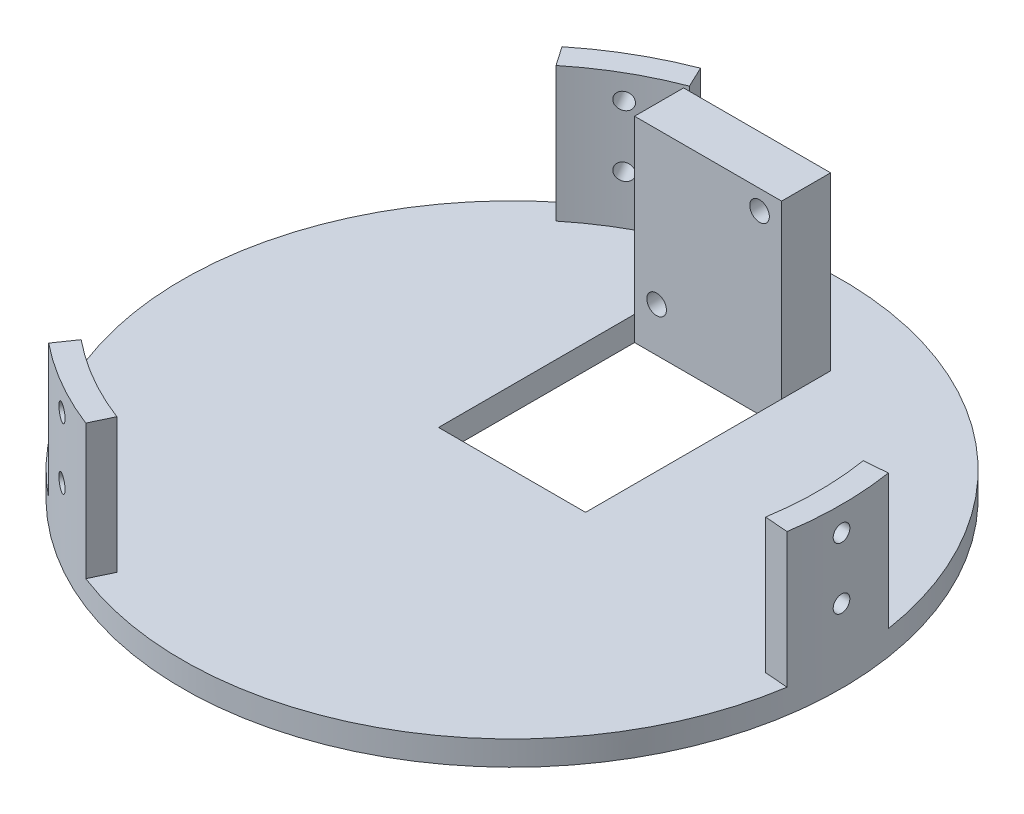
SolidWorks part; units mm, degrees
material "6061-T6 (SS)"
ref_plane "Front" through (0, 0, 0) normal (0, 0, 1) x (1, 0, 0)
ref_plane "Top" through (0, 0, 0) normal (0, 1, 0) x (1, 0, 0)
ref_plane "Right" through (0, 0, 0) normal (1, 0, 0) x (0, 0, -1)
sketch "Sketch1" plane through (0, 0, 0) normal (0, 1, 0) x (1, 0, 0)
  line L1 (0, 0) -> (127.635, 0)
  line L2 (0, 0) -> (0, 127.635)
  line L3 (0, 127.635) -> (127.635, 127.635)
  line L4 (127.635, 0) -> (127.635, 127.635)
  dimension "D1" = 127.635
  dimension "D2" = 127.635
extrude "Main Plate" add sketch "Sketch1" along normal blind 6.35
sketch "Sketch9" plane through (0, 6.35, 0) normal (0, 1, 0) x (1, 0, 0)
  circle A0 centre (63.8175, 63.8175) radius 85.725
  dimension "D1" = 171.45
extrude "Boss-Extrude1" add sketch "Sketch9" against normal up to surface (6.35 mm away) contours A0 up to face at (63.8175, 0, -63.8175)
sketch "Sketch10" plane through (0, 6.35, 0) normal (0, 1, 0) x (1, 0, 0)
  circle A0 centre (63.8175, 63.8175) radius 95.25
  circle A1 centre (63.8175, 63.8175) radius 85.4075
  dimension "D1" = 170.815
  dimension "D2" = 190.5
extrude "Cut-Extrude1" cut sketch "Sketch10" against normal blind 167.64 contours A0 | A1
sketch "Sketch14" plane through (0, 6.35, 0) normal (0, 1, 0) x (1, 0, 0)
  line L0 (201.1692, 63.8175) -> (-73.4523, 63.8175) construction
ref_plane "Plane1" through (0, 0, -63.8175) normal (0, 0, -1) x (-1, 0, 0)
ref_plane "Plane3" through (0, 3.175, 0) normal (0, 1, 0) x (1, 0, 0)
ref_plane "Plane2" through (-21.59, 0, 0) normal (-1, 0, 0) x (0, 0, 1)
sketch "Sketch18" plane through (0, 3.175, 0) normal (0, 1, 0) x (1, 0, 0)
  circle A0 centre (63.8175, 63.8175) radius 85.4075
  circle A1 centre (63.8175, 63.8175) radius 79.375
  circle A4 centre (63.8175, 63.8175) radius 85.4075 construction
  dimension "D1" = 158.75
extrude "Boss-Extrude2" add sketch "Sketch18" along normal blind 38.1
sketch "Sketch20" plane through (0, 6.35, 0) normal (0, 1, 0) x (1, 0, 0)
  line L0 (63.8175, 143.1925) -> (63.8175, -15.5575) construction
  line L1 (-15.5575, 63.8175) -> (143.1925, 63.8175) construction
  line L2 (63.8175, 63.8175) -> (-15.5575, -73.664) construction
  circle A0 centre (63.8175, 63.8175) radius 79.375 construction
  dimension "D1" = 30
ref_plane "Plane5" through (-15.5575, 6.35, 73.664) normal (-0.5, 0, 0.866) x (0.866, 0, 0.5)
sketch "Sketch15" plane through (166.2216, -6.35, 178.6143) normal (0.5, 0, -0.866) x (-0.866, 0, -0.5)
  line L3 (289.2754, 47.625) -> (130.5254, 47.625) construction
  circle A0 centre (209.9004, 25.4) radius 2.159
  circle A1 centre (209.9004, 41.275) radius 2.159
  dimension "D1" = 4.318
  dimension "D2" = 15.875
  dimension "D3" = 4.318
  dimension "D6" = 6.35
extrude "Cut-Extrude3" cut sketch "Sketch15" along normal blind 88.9
pattern_circular "CirPattern1" count 3 over 360 about axis through (63.8175, -161.29, -63.8175) along (0, 1, 0) of "Cut-Extrude3" reverse direction yes
ref_plane "Plane4" through (63.8175, 0, 0) normal (-1, 0, 0) x (0, 0, 1)
sketch "Sketch23" plane through (0, 6.35, 0) normal (0, 1, 0) x (1, 0, 0)
  line L0 (13.6787, 125.352) -> (7.5523, 134.2379)
  line L1 (15.1867, 11.8815) -> (13.6787, 2.283) construction
  line L3 (-15.5575, 63.8175) -> (143.1925, 63.8175) construction
  line L4 (63.8175, 143.1925) -> (63.8175, -15.5575) construction
  line L5 (-15.5575, 63.8175) -> (143.1925, 63.8175)
  line L6 (63.8175, 143.1925) -> (63.8175, -15.5575)
  line L7 (13.6787, 2.283) -> (6.9592, -7.4631)
  line L8 (-19.2671, 125.3206) -> (-48.797, 60.3978)
  line L9 (-48.797, 60.3978) -> (-9.8843, 7.0525)
  line L10 (-9.8843, 7.0525) -> (6.9592, -7.4631)
  line L11 (24.1345, -4.9259) -> (13.6787, 2.283) construction
  line L14 (7.5523, 134.2379) -> (-19.2671, 125.3206)
  line L15 (24.1345, 132.5609) -> (13.6787, 125.352) construction
  line L28 (63.8175, 63.8175) -> (24.1345, -4.9259) construction
  line L29 (63.8175, 63.8175) -> (24.1345, 132.5609) construction
  line L30 (142.1773, 76.4717) -> (152.9359, 77.3344)
  line L31 (152.9359, 77.3344) -> (158.6231, 105.0193)
  line L32 (158.6231, 105.0193) -> (117.1632, 163.0543)
  line L33 (117.1632, 163.0543) -> (51.5085, 156.0277)
  line L34 (51.5085, 156.0277) -> (30.5159, 148.6985)
  line L35 (35.5964, 138.0062) -> (30.5159, 148.6985)
  line L36 (35.5964, -10.3712) -> (30.9643, -20.1198)
  line L37 (30.9643, -20.1198) -> (52.0965, -38.8874)
  line L38 (52.0965, -38.8874) -> (123.0863, -31.9996)
  line L39 (123.0863, -31.9996) -> (149.8284, 28.3723)
  line L40 (149.8284, 28.3723) -> (153.9775, 50.217)
  line L41 (142.1773, 51.1633) -> (153.9775, 50.217)
  circle A0 centre (63.8175, 63.8175) radius 79.375 construction
  arc A1 (13.6787, 2.283) -> (13.6787, 125.352) centre (63.8175, 63.8175) cw
  circle A3 centre (63.8175, 63.8175) radius 79.375
  arc A6 (35.5964, 138.0062) -> (142.1773, 76.4717) centre (63.8175, 63.8175) cw
  arc A7 (142.1773, 51.1633) -> (35.5964, -10.3712) centre (63.8175, 63.8175) cw
  circle A9 centre (63.8175, 63.8175) radius 79.375
  circle M15 centre (63.8175, 63.8175) radius 79.375
  dimension "D1" = 79.375
  dimension "D2" = 0
  dimension "D3" = 12.7
  dimension "D4" = 90
  dimension "D5" = 12.7
  dimension "D6" = 90
  dimension "D8" = 60.004
  dimension "D9" = 60.004
  dimension "D7" = 3
extrude "Cut-Extrude6" cut sketch "Sketch23" along normal blind 111.6 contours L9 L10 L7 L8 M15 | L34 L35 A6 L30 L31 L32 L33 | L40 L41 A7 L36 L37 L38 L39 region at (-18.2379, 6.35, -69.3048)
sketch "Sketch24" plane through (0, 6.35, 0) normal (0, 1, 0) x (1, 0, 0)
  line L1 (44.7675, 114.6175) -> (82.8675, 114.6175)
  line L2 (44.7675, 114.6175) -> (44.7675, 63.8175)
  line L3 (44.7675, 63.8175) -> (82.8675, 63.8175)
  line L4 (82.8675, 114.6175) -> (82.8675, 63.8175)
  line L5 (44.7675, 114.6175) -> (82.8675, 63.8175) construction
  line L6 (44.7675, 63.8175) -> (82.8675, 114.6175) construction
  arc A0 (148.2085, 76.9553) -> (32.9997, 143.4712) centre (63.8175, 63.8175) ccw construction
  arc A1 (148.2085, 76.9553) -> (32.9997, 143.4712) centre (63.8175, 63.8175) ccw
  point P0 (63.8175, 89.2175)
  point P8 (0, 0)
  point P9 (67.985, 93.1436)
  dimension "D1" = 50.8
  dimension "D2" = 38.1
  dimension "D3" = 25.4
  dimension "D4" = 0
extrude "Cut-Extrude7" cut sketch "Sketch24" against normal through all contours L4 L1 L2 L3 region at (63.8175, 6.35, -89.2175)
sketch "Sketch25" plane through (0, 6.35, 0) normal (0, 1, 0) x (1, 0, 0)
  line L1 (44.7675, 127.3175) -> (82.8675, 127.3175)
  line L2 (44.7675, 127.3175) -> (44.7675, 114.6175)
  line L3 (44.7675, 114.6175) -> (82.8675, 114.6175)
  line L4 (82.8675, 127.3175) -> (82.8675, 114.6175)
  line L5 (44.7675, 127.3175) -> (82.8675, 114.6175) construction
  line L6 (44.7675, 114.6175) -> (82.8675, 127.3175) construction
  point P0 (63.8175, 120.9675)
  dimension "D1" = 12.7
extrude "Boss-Extrude3" add sketch "Sketch25" along normal blind 44.45
sketch "Sketch26" plane through (0, 0, -114.6175) normal (0, 0, 1) x (1, 0, 0)
  line L1 (44.7675, 50.8) -> (82.8675, 50.8) construction
  line L2 (82.8675, 50.8) -> (82.8675, 6.35) construction
  circle A0 centre (77.1525, 45.72) radius 2.54
  circle A1 centre (50.4825, 11.43) radius 2.54
  dimension "D1" = 5.08
  dimension "D2" = 5.715
  dimension "D3" = 34.29
  dimension "D4" = 5.08
  dimension "D5" = 26.67
extrude "Cut-Extrude8" cut sketch "Sketch26" against normal blind 44.45
